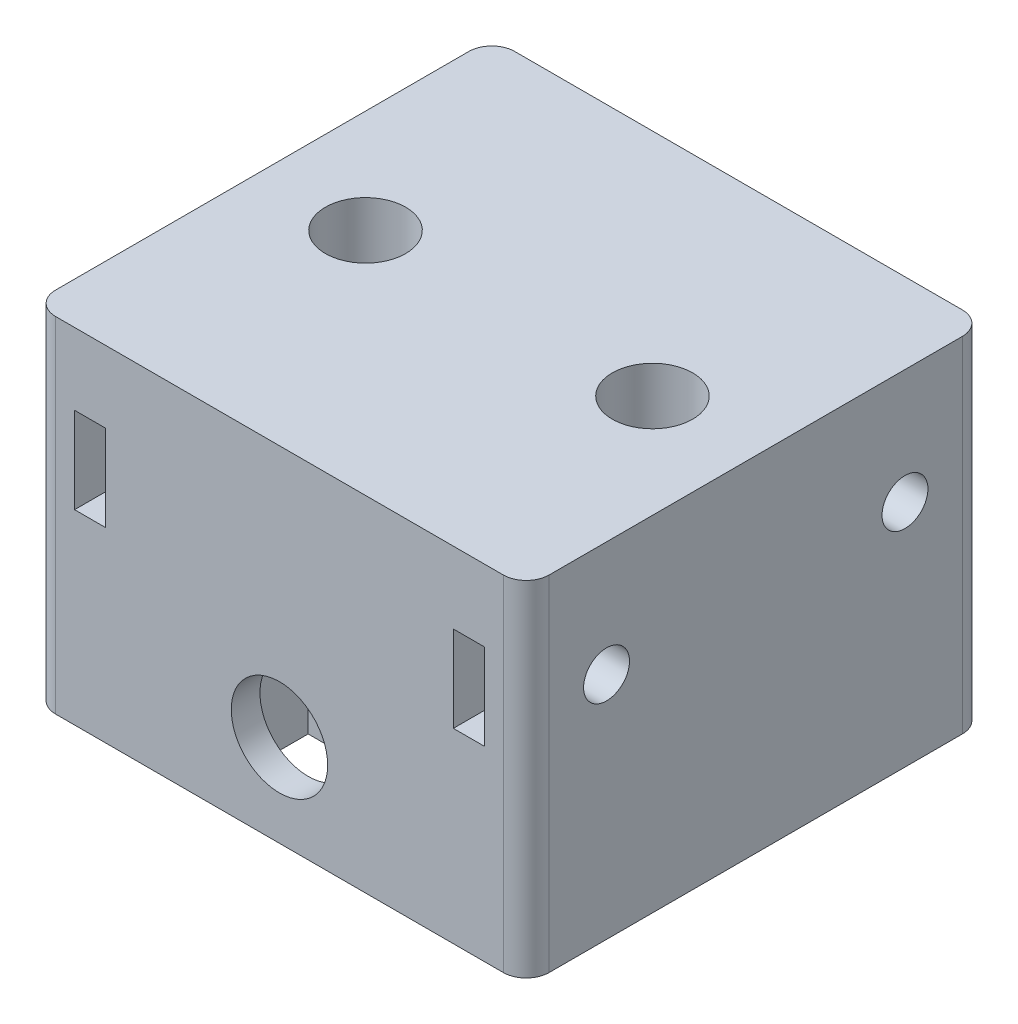
SolidWorks part; units mm, degrees
ref_plane "Front Plane" through (0, 0, 0) normal (0, 0, 1) x (1, 0, 0)
ref_plane "Top Plane" through (0, 0, 0) normal (0, 1, 0) x (1, 0, 0)
ref_plane "Right Plane" through (0, 0, 0) normal (1, 0, 0) x (0, 0, -1)
sketch "Sketch1" plane through (0, 23.2658, 0) normal (0, -1, 0) x (1, 0, 0)
  line L0 (-872.8528, 426.7861) -> (-952.8528, 426.7861) construction
  line L1 (-957.8528, 466.7861) -> (-912.8528, 466.7861)
  line L2 (-957.8528, 466.7861) -> (-957.8528, 426.7861)
  line L3 (-957.8528, 426.7861) -> (-912.8528, 426.7861)
  line L4 (-912.8528, 466.7861) -> (-912.8528, 426.7861)
  line L5 (-952.8528, 466.7861) -> (-872.8528, 466.7861) construction
  dimension "D1" = 45
extrude "Boss-Extrude1" add sketch "Sketch1" along normal blind 30
sketch "Sketch2" plane through (0, -6.7342, 0) normal (0, -1, 0) x (1, 0, 0)
  line L1 (-922.8528, 453.1369) -> (-928.3528, 449.9615)
  line L2 (-928.3528, 449.9615) -> (-928.3528, 443.6107)
  line L3 (-928.3528, 443.6107) -> (-922.8528, 440.4352)
  line L4 (-922.8528, 440.4352) -> (-917.3528, 443.6107)
  line L5 (-917.3528, 443.6107) -> (-917.3528, 449.9615)
  line L6 (-917.3528, 449.9615) -> (-922.8528, 453.1369)
  line L7 (-947.8528, 453.1369) -> (-953.3528, 449.9615)
  line L8 (-953.3528, 449.9615) -> (-953.3528, 443.6107)
  line L9 (-953.3528, 443.6107) -> (-947.8528, 440.4352)
  line L10 (-947.8528, 440.4352) -> (-942.3528, 443.6107)
  line L11 (-942.3528, 443.6107) -> (-942.3528, 449.9615)
  line L12 (-942.3528, 449.9615) -> (-947.8528, 453.1369)
  circle A0 centre (-922.8528, 446.7861) radius 5.5 construction
  circle A1 centre (-947.8528, 446.7861) radius 5.5 construction
  dimension "D1" = 11
extrude "Cut-Extrude1" cut sketch "Sketch2" against normal blind 25
sketch "Sketch3" plane through (0, 0, 426.7861) normal (0, 0, -1) x (-1, 0, 0)
  line L0 (912.8528, 1.2658) -> (957.8528, 1.2658) construction
  line L1 (912.8528, -6.7342) -> (912.8528, 23.2658) construction
  line L2 (957.8528, -6.7342) -> (957.8528, 23.2658) construction
  line L3 (957.8528, -6.7342) -> (912.8528, -6.7342) construction
  line L4 (931.8578, 1.1773) -> (933.1143, 1.1773)
  circle A0 centre (935.3528, 1.2658) radius 2
  dimension "D2" = 4
  dimension "D1" = 8
extrude "Cut-Extrude2" cut sketch "Sketch3" against normal through all contours A0
sketch "Sketch7" plane through (-957.8528, 0, 0) normal (-1, 0, 0) x (0, 0, 1)
  line L0 (433.7861, 13.2658) -> (459.7861, 13.2658) construction
  line L1 (426.7861, -6.7342) -> (426.7861, 23.2658) construction
  line L2 (466.7861, -6.7342) -> (466.7861, 23.2658) construction
  line L4 (466.7861, 23.2658) -> (426.7861, 23.2658) construction
  circle A0 centre (433.7861, 13.2658) radius 2
  circle A1 centre (459.7861, 13.2658) radius 2
  dimension "D4" = 4
  dimension "D1" = 7
  dimension "D2" = 7
  dimension "D3" = 10
extrude "Cut-Extrude4" cut sketch "Sketch7" against normal through all
sketch "Sketch6" plane through (0, -6.7342, 0) normal (0, -1, 0) x (1, 0, 0)
  line L0 (-935.3528, 466.7861) -> (-935.3528, 426.7861) construction
  line L1 (-912.8528, 466.7861) -> (-957.8528, 466.7861) construction
  line L2 (-957.8528, 426.7861) -> (-912.8528, 426.7861) construction
  line L4 (-931.6028, 429.4361) -> (-939.1028, 429.4361)
  line L5 (-931.6028, 429.4361) -> (-931.6028, 432.1361)
  line L6 (-931.6028, 432.1361) -> (-939.1028, 432.1361)
  line L7 (-939.1028, 429.4361) -> (-939.1028, 432.1361)
  line L8 (-931.6028, 429.4361) -> (-939.1028, 432.1361) construction
  line L9 (-931.6028, 432.1361) -> (-939.1028, 429.4361) construction
  line L10 (-931.6028, 461.4361) -> (-939.1028, 461.4361)
  line L11 (-931.6028, 461.4361) -> (-931.6028, 464.1361)
  line L12 (-931.6028, 464.1361) -> (-939.1028, 464.1361)
  line L13 (-939.1028, 461.4361) -> (-939.1028, 464.1361)
  line L14 (-931.6028, 461.4361) -> (-939.1028, 464.1361) construction
  line L15 (-931.6028, 464.1361) -> (-939.1028, 461.4361) construction
  point P6 (-935.3528, 430.7861)
  point P11 (-935.3528, 462.7861)
  dimension "D1" = 7.5
  dimension "D2" = 2.7
  dimension "D3" = 4
  dimension "D4" = 4
extrude "Cut-Extrude3" [suppressed] cut sketch "Sketch6" against normal blind 11.75
sketch "Sketch9" plane through (0, 0, 426.7861) normal (0, 0, -1) x (-1, 0, 0)
  line L0 (918.8528, 13.2658) -> (951.8528, 13.2658) construction
  line L1 (917.5028, 17.0158) -> (920.2028, 17.0158)
  line L2 (917.5028, 17.0158) -> (917.5028, 9.5158)
  line L3 (917.5028, 9.5158) -> (920.2028, 9.5158)
  line L4 (920.2028, 17.0158) -> (920.2028, 9.5158)
  line L5 (917.5028, 17.0158) -> (920.2028, 9.5158) construction
  line L6 (917.5028, 9.5158) -> (920.2028, 17.0158) construction
  line L7 (950.5028, 17.0158) -> (953.2028, 17.0158)
  line L8 (950.5028, 17.0158) -> (950.5028, 9.5158)
  line L9 (950.5028, 9.5158) -> (953.2028, 9.5158)
  line L10 (953.2028, 17.0158) -> (953.2028, 9.5158)
  line L11 (950.5028, 17.0158) -> (953.2028, 9.5158) construction
  line L12 (950.5028, 9.5158) -> (953.2028, 17.0158) construction
  line L13 (957.8528, 15.2658) -> (912.8528, 15.2658) construction
  line L14 (912.8528, 11.2658) -> (957.8528, 11.2658) construction
  line L17 (912.8528, -6.7342) -> (912.8528, 23.2658) construction
  line L18 (957.8528, -6.7342) -> (957.8528, 23.2658) construction
  point P0 (918.8528, 13.2658)
  point P5 (951.8528, 13.2658)
  dimension "D1" = 7.5
  dimension "D2" = 2.7
  dimension "D3" = 6
  dimension "D4" = 6
extrude "Cut-Extrude5" cut sketch "Sketch9" against normal blind 10.75
extrude "Cut-Extrude6" cut sketch "Sketch9<2>" along normal blind 10.75 from surface starting at face at (-937.3528, 1.2658, 466.7861)
sketch "Sketch9<2>" plane through (0, 0, 426.7861) normal (0, 0, -1) x (-1, 0, 0) same geometry as "Sketch9"
sketch "Sketch10" plane through (0, -6.7342, 0) normal (0, -1, 0) x (1, 0, 0)
  circle A0 centre (-947.8528, 446.7861) radius 3.5
  circle A1 centre (-922.8528, 446.7861) radius 3.5
  dimension "D1" = 7
  dimension "D2" = 7
extrude "Cut-Extrude9" cut sketch "Sketch10" against normal through all
sketch "Sketch11" plane through (-957.8528, 0, 0) normal (-1, 0, 0) x (0, 0, 1)
  line L1 (430.0361, 17.0158) -> (437.5361, 17.0158)
  line L2 (430.0361, 17.0158) -> (430.0361, 9.5158)
  line L3 (430.0361, 9.5158) -> (437.5361, 9.5158)
  line L4 (437.5361, 17.0158) -> (437.5361, 9.5158)
  line L5 (430.0361, 17.0158) -> (437.5361, 9.5158) construction
  line L6 (430.0361, 9.5158) -> (437.5361, 17.0158) construction
  line L7 (456.0361, 17.0158) -> (463.5361, 17.0158)
  line L8 (456.0361, 17.0158) -> (456.0361, 9.5158)
  line L9 (456.0361, 9.5158) -> (463.5361, 9.5158)
  line L10 (463.5361, 17.0158) -> (463.5361, 9.5158)
  line L11 (456.0361, 17.0158) -> (463.5361, 9.5158) construction
  line L12 (456.0361, 9.5158) -> (463.5361, 17.0158) construction
  point P0 (433.7861, 13.2658)
  point P6 (459.7861, 13.2658)
  dimension "D1" = 7.5
  dimension "D2" = 7.5
sketch "Sketch12" plane through (0, 0, 466.7861) normal (0, 0, 1) x (1, 0, 0)
  line L1 (-939.1028, 5.0158) -> (-931.6028, 5.0158)
  line L2 (-939.1028, 5.0158) -> (-939.1028, -2.4842)
  line L3 (-939.1028, -2.4842) -> (-931.6028, -2.4842)
  line L4 (-931.6028, 5.0158) -> (-931.6028, -2.4842)
  line L5 (-939.1028, 5.0158) -> (-931.6028, -2.4842) construction
  line L6 (-939.1028, -2.4842) -> (-931.6028, 5.0158) construction
  point P0 (-935.3528, 1.2658)
  dimension "D1" = 7.5
  dimension "D2" = 7.5
sketch "Sketch13" plane through (0, 0, 466.7861) normal (0, 0, 1) x (1, 0, 0)
  circle A0 centre (-935.3528, 1.2658) radius 4.2
  dimension "D1" = 8.4
extrude "Cut-Extrude10" cut sketch "Sketch13" against normal through all
sketch "Sketch14" plane through (0, 0, 426.7861) normal (0, 0, -1) x (-1, 0, 0)
  line L0 (957.8528, -6.7342) -> (912.8528, -6.7342) construction
  line L1 (913.8528, -6.7342) -> (956.8528, -6.7342)
  line L2 (913.8528, -6.7342) -> (913.8528, 23.2658)
  line L3 (913.8528, 23.2658) -> (956.8528, 23.2658)
  line L4 (956.8528, -6.7342) -> (956.8528, 23.2658)
  line L5 (957.8528, 23.2658) -> (912.8528, 23.2658) construction
  line L6 (912.8528, -6.7342) -> (912.8528, 23.2658) construction
  dimension "D1" = 1
  dimension "D2" = 1
extrude "Cut-Extrude11" cut sketch "Sketch14" against normal through all flip side to cut
fillet "Fillet1" radius 2 4 edges at (-913.8528, 8.2658, 466.7861) (-956.8528, 8.2658, 466.7861) (-913.8528, 8.2658, 426.7861) (-956.8528, 8.2658, 426.7861)
sketch "Sketch15" plane through (0, -6.7342, 0) normal (0, -1, 0) x (1, 0, 0)
  line L1 (-942.3528, 464.2861) -> (-928.3528, 464.2861)
  line L2 (-942.3528, 464.2861) -> (-942.3528, 457.2861)
  line L3 (-942.3528, 457.2861) -> (-928.3528, 457.2861)
  line L4 (-928.3528, 464.2861) -> (-928.3528, 457.2861)
  line L5 (-942.3528, 464.2861) -> (-928.3528, 457.2861) construction
  line L6 (-942.3528, 457.2861) -> (-928.3528, 464.2861) construction
  line L8 (-935.3528, 466.7861) -> (-935.3528, 426.7861) construction
  line L9 (-915.8528, 466.7861) -> (-954.8528, 466.7861) construction
  line L10 (-954.8528, 426.7861) -> (-915.8528, 426.7861) construction
  point P0 (-935.3528, 460.7861)
  dimension "D1" = 6
  dimension "D2" = 7
  dimension "D3" = 14
extrude "Cut-Extrude12" cut sketch "Sketch15" against normal blind 10
sketch "Sketch16" plane through (0, 0, 457.2861) normal (0, 0, 1) x (1, 0, 0)
  line L0 (-928.3528, 3.2658) -> (-928.3528, -6.7342) construction
  line L1 (-928.3528, 5.3073) -> (-935.3528, 9.3487)
  line L2 (-935.3528, 9.3487) -> (-942.3528, 5.3073)
  line L3 (-942.3528, 5.3073) -> (-942.3528, -2.7756)
  line L4 (-942.3528, -2.7756) -> (-935.3528, -6.8171)
  line L5 (-935.3528, -6.8171) -> (-928.3528, -2.7756)
  line L6 (-928.3528, -2.7756) -> (-928.3528, 5.3073)
  circle A0 centre (-935.3528, 1.2658) radius 7 construction
extrude "Cut-Extrude13" cut sketch "Sketch16" along normal up to surface (7 mm away) up to face at (-935.3528, -1.1009, 464.2861)
